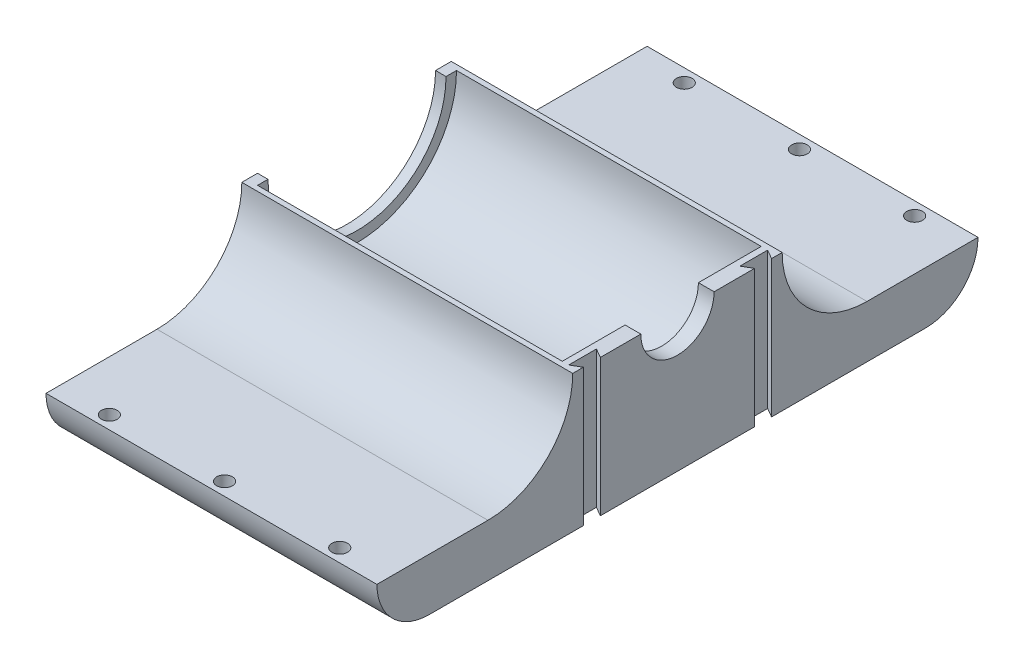
SolidWorks part; units mm, degrees
ref_plane "Front Plane" through (0, 0, 0) normal (0, 0, 1) x (1, 0, 0)
ref_plane "Top Plane" through (0, 0, 0) normal (0, 1, 0) x (1, 0, 0)
ref_plane "Right Plane" through (0, 0, 0) normal (1, 0, 0) x (0, 0, -1)
sketch "Sketch1" plane through (0, 0, 0) normal (1, 0, 0) x (0, 0, -1)
  line L0 (57.4, 42.0261) -> (57.4, 0) construction
  line L1 (0, 0) -> (114.8, 0)
  line L2 (0, 0) -> (0, 26.2)
  line L3 (114.8, 0) -> (114.8, 26.2)
  line L4 (0, 26.2) -> (5, 26.2) construction
  line L6 (37.4, 26.2) -> (77.4, 26.2) construction
  line L7 (37.4, 26.2) -> (77.4, 26.2)
  line L8 (0, 26.2) -> (5, 26.2)
  line L10 (37.4, 26.2) -> (77.4, 26.2)
  line L11 (109.8, 26.2) -> (114.8, 26.2)
  arc A0 (5, 26.2) -> (37.4, 26.2) centre (21.2, 26.2) ccw
  arc A1 (77.4, 26.2) -> (109.8, 26.2) centre (93.6, 26.2) ccw
  circle A2 centre (57.4, 13.245) radius 62.5 construction
  point P15 (93.6, 10)
  dimension "D4" = 16.2
  dimension "D3" = 16.2
  dimension "D6" = 125
  dimension "D1" = 5
  dimension "D5" = 10
  dimension "D2" = 40
extrude "Boss-Extrude1" add sketch "Sketch1" along normal blind 63.2 contours L8 L2 L1 L3 L7 region at (0, 10.7494, -57.4)
sketch "Sketch30" plane through (0, 26.2, 0) normal (0, 1, 0) x (1, 0, 0)
  line L0 (63.2, 57.4) -> (17.5829, 57.4) construction
  line L1 (63.2, 37.4) -> (63.2, 77.4) construction
  line L2 (63.2, 75.375) -> (61.4246, 76.4)
  line L3 (61.4246, 76.4) -> (61.4246, 71.1)
  line L4 (61.4246, 71.1) -> (63.2, 72.125)
  line L5 (63.2, 42.675) -> (61.4246, 43.7)
  line L6 (61.4246, 43.7) -> (61.4246, 38.4)
  line L7 (61.4246, 38.4) -> (63.2, 39.425)
  line L8 (63.2, 75.375) -> (63.2, 72.125)
  line L9 (63.2, 42.675) -> (63.2, 39.425)
  line L10 (63.2, 77.4) -> (0, 77.4) construction
  line L12 (63.2, 37.4) -> (0, 37.4) construction
  dimension "D1" = 5.3
  dimension "D2" = 60
  dimension "D3" = 60
  dimension "D4" = 3.25
  dimension "D5" = 60
  dimension "D6" = 1
  dimension "D7" = 1
extrude "Cut-Extrude14" cut sketch "Sketch30" against normal up to next
sketch "Sketch31" plane through (0, 0, 0) normal (-1, 0, 0) x (0, 0, 1)
  line L0 (-37.4, 26.2) -> (-77.4, 26.2) construction
  circle A0 centre (-57.4, 26.2) radius 19
  dimension "D1" = 38
extrude "Cut-Extrude15" cut sketch "Sketch31" against normal offset from surface (60.2 mm away) 3 contours A0 up to face at (63.2, 13.1, -57.4)
sketch "Sketch32" plane through (63.2, 0, 0) normal (1, 0, 0) x (0, 0, -1)
  line L0 (42.675, 26.2) -> (72.125, 26.2) construction
  circle A0 centre (57.4, 26.2) radius 7
  dimension "D1" = 14
extrude "Cut-Extrude16" cut sketch "Sketch32" against normal up to next
sketch "Sketch33" plane through (0, 0, 0) normal (-1, 0, 0) x (0, 0, 1)
  line L0 (-74.4, 26.2) -> (-76.4, 26.2)
  line L1 (-40.4, 26.2) -> (-38.4, 26.2)
  arc A1 (-76.4, 26.2) -> (-38.4, 26.2) centre (-57.4, 26.2) ccw construction
  arc A2 (-74.4, 26.2) -> (-40.4, 26.2) centre (-57.4, 26.2) ccw
  arc A3 (-74.4, 26.2) -> (-40.4, 26.2) centre (-57.4, 26.2) ccw
  arc A4 (-76.4, 26.2) -> (-38.4, 26.2) centre (-57.4, 26.2) ccw
  dimension "D1" = 2
extrude "Boss-Extrude6" add sketch "Sketch33" against normal blind 2
fillet "Fillet1" radius 10 2 edges at (31.6, 0, -114.8) (31.6, 0, 0)
sketch "Sketch34" plane through (0, 26.2, 0) normal (0, 1, 0) x (1, 0, 0)
  line L0 (0, 112.3) -> (63.2, 112.3) construction
  line L1 (0, 109.8) -> (0, 114.8) construction
  line L2 (63.2, 109.8) -> (63.2, 114.8) construction
  line L3 (63.2, 57.4) -> (76.2618, 57.4) construction
  line L4 (63.2, 50.4) -> (63.2, 64.4) construction
  circle A0 centre (9.6, 112.3) radius 1.5
  circle A1 centre (31.6, 112.3) radius 1.5
  circle A2 centre (53.6, 112.3) radius 1.5
  circle A3 centre (53.6, 2.5) radius 1.5
  circle A4 centre (31.6, 2.5) radius 1.5
  circle A5 centre (9.6, 2.5) radius 1.5
  dimension "D1" = 3
  dimension "D2" = 22
  dimension "D3" = 22
extrude "Cut-Extrude17" cut sketch "Sketch34" against normal blind 20
sketch "Sketch35" plane through (0, 0, 0) normal (0, -1, 0) x (1, 0, 0)
  line L0 (31.6, -10) -> (31.6, -104.8) construction
  line L1 (16.35, -29.9) -> (46.85, -29.9) construction
  line L2 (16.35, -29.9) -> (16.35, -84.9) construction
  line L3 (16.35, -84.9) -> (46.85, -84.9) construction
  line L4 (46.85, -29.9) -> (46.85, -84.9) construction
  line L5 (63.2, -10) -> (0, -10) construction
  line L6 (0, -104.8) -> (63.2, -104.8) construction
  line L10 (16.35, -57.4) -> (0, -57.4) construction
  line L11 (0, -10) -> (0, -104.8) construction
  circle A0 centre (16.35, -29.9) radius 2.3
  circle A1 centre (46.85, -29.9) radius 2.3
  circle A2 centre (16.35, -84.9) radius 2.3
  circle A3 centre (46.85, -84.9) radius 2.3
  point P8 (31.6, -29.9)
  dimension "D1" = 4.6
  dimension "D2" = 4.6
  dimension "D3" = 4.6
  dimension "D4" = 4.6
  dimension "D5" = 55
  dimension "D6" = 30.5
extrude "Cut-Extrude18" cut sketch "Sketch35" against normal blind 6
sketch "Sketch36" plane through (63.2, 0, 0) normal (1, 0, 0) x (0, 0, -1)
  line L0 (21.2, 10) -> (0, 10)
  line L1 (0, 10) -> (0, 26.2)
  line L2 (0, 26.2) -> (5, 26.2)
  line L3 (0, 26.2) -> (5, 26.2) construction
  line L4 (57.4, 19.2) -> (57.4, 39.0886) construction
  line L5 (114.8, 26.2) -> (109.8, 26.2)
  line L6 (114.8, 10) -> (114.8, 26.2)
  line L7 (93.6, 10) -> (114.8, 10)
  arc A0 (5, 26.2) -> (37.4, 26.2) centre (21.2, 26.2) ccw construction
  arc A1 (5, 26.2) -> (21.2, 10) centre (21.2, 26.2) ccw
  arc A2 (50.4, 26.2) -> (64.4, 26.2) centre (57.4, 26.2) ccw construction
  arc A3 (109.8, 26.2) -> (93.6, 10) centre (93.6, 26.2) cw
extrude "Cut-Extrude19" cut sketch "Sketch36" against normal up to next
equation "\"MotorDIA\"= 37' Motor Diameter"
equation "\"SyringeDIA\"= 31.4'60ml Syringe Diameter"
equation "\"MotorShaftDIA\"= 6'Motor Shaft Dia"
equation "\"MotorKeyway\"= 1'Motor Shaft Keyway Depth"
equation "\"MotorLength\"= 56.7'Motor Length Excluding Shaft"
equation "\"SyringeLength\"= 117.3'60ml Syringe Length Excluding Nozzle"
equation "\"3Dtol\"= .5'Sizing Tolerance for 3D printed parts"
equation "\"ChamberDIA\"= 100 - 4'Buoyancy Chamber inner Diameter"
equation "\"ChamberThk\"= 2mm'Buoyancy Chamber Wall Thickness"
equation "\"D1@Boss-Extrude1\"=\"MotorLength\"+\"3Dtol\"+4"
equation "\"BearingOD\"= 10"
equation "\"BearingID\"= 4"
equation "\"Bearingwidth\"= 4"
equation "\"ShaftDIA\"= 4"
equation "\"D3@Sketch1\"=\"D4@Sketch1\""
